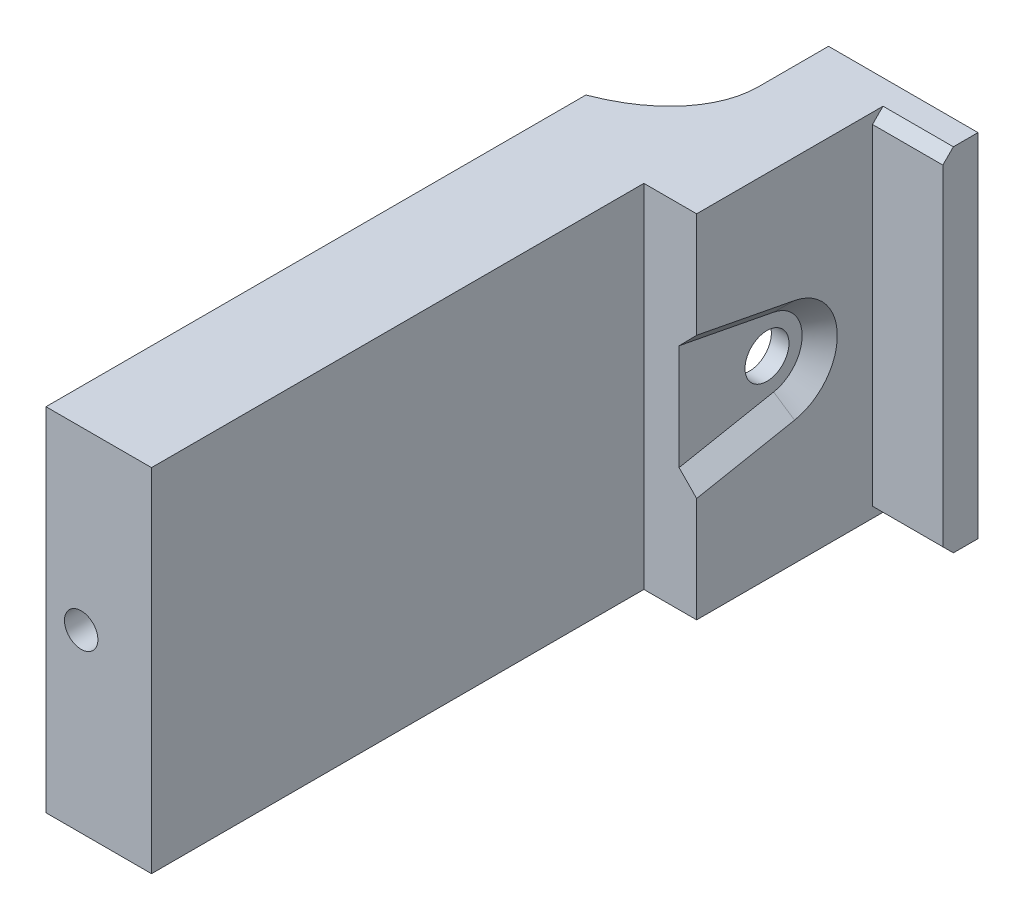
SolidWorks part; units mm, degrees
ref_plane "前视基准面" through (0, 0, 0) normal (0, 0, 1) x (1, 0, 0)
ref_plane "上视基准面" through (0, 0, 0) normal (0, 1, 0) x (1, 0, 0)
ref_plane "右视基准面" through (0, 0, 0) normal (1, 0, 0) x (0, 0, -1)
other "Configuration Table"
sketch "草图1" plane through (0, 0, 0) normal (0, 1, 0) x (1, 0, 0)
  line L0 (0, 0) -> (3, 0)
  line L1 (3, 0) -> (3, 10)
  line L2 (3, 10) -> (1, 10)
  line L3 (1, 10) -> (1, 2)
  line L4 (1, 2) -> (-2, 2)
  line L6 (-2, -26) -> (-6, -26)
  line L7 (-6, -26) -> (-6, -28)
  line L8 (-6, -28) -> (0, -28)
  line L9 (0, -28) -> (0, 0)
  line L12 (-2, 2) -> (-2, -26)
  dimension "D1" = 8
  dimension "D2" = 4
  dimension "D3" = 28
  dimension "D4" = 2
  dimension "D5" = 2
  dimension "D6" = 3
  dimension "D7" = 2
  dimension "D8" = 2
extrude "凸台-拉伸1" add sketch "草图1" along normal mid plane 20
sketch "草图2" plane through (1, 0, 0) normal (-1, 0, 0) x (0, 0, 1)
  line L0 (-5, 17.2009) -> (-5, -18.1104) construction
  line L2 (0, 0) -> (-13.8262, 0) construction
  line L3 (-2, 10) -> (-2, -10) construction
  circle A0 centre (-5, 0) radius 1.25
  dimension "D2" = 2.5
  dimension "D1" = 3
extrude "切除-拉伸1" cut sketch "草图2" against normal blind 15
sketch "草图4" plane through (0, 0, 28) normal (0, 0, 1) x (1, 0, 0)
  line L0 (-6, 0) -> (6.5775, 0) construction
  line L1 (-6, 10) -> (-6, -10) construction
  line L2 (-4, 12.0932) -> (-4, -13.8811) construction
  circle A0 centre (-4, 0) radius 0.95
  dimension "D2" = 1.9
  dimension "D1" = 2
extrude "切除-拉伸2" cut sketch "草图4" against normal through all
sketch "草图5" plane through (0, 0, 26) normal (0, 0, -1) x (-1, 0, 0)
  line L0 (2, 10) -> (6, 10)
  line L1 (6, 10) -> (6, -10) construction
  line L2 (2, 10) -> (6, 10) construction
  line L3 (6, 10) -> (2, 6)
  line L4 (2, 10) -> (2, -10) construction
  line L5 (2, 6) -> (2, 10)
  line L6 (0, 0) -> (10.5459, 0) construction
  line L7 (2, -6) -> (2, -10)
  line L8 (6, -10) -> (2, -6)
  line L9 (2, -10) -> (6, -10)
  dimension "D1" = 45
extrude "凸台-拉伸2" add sketch "草图5" along normal up to surface (28 mm away) up to face at (-0.5, 0, -2)
sketch "草图7" plane through (0, 0, -10) normal (0, 0, -1) x (-1, 0, 0)
  line L0 (-1, -10) -> (6, -10) construction
  line L1 (-1, 10) -> (-7, 10)
  line L2 (-1, 10) -> (-1, -10)
  line L3 (-1, -10) -> (-7, -10)
  line L4 (-7, 10) -> (-7, -10)
  line L5 (-1, 10) -> (-1, -10) construction
  dimension "D1" = 6
extrude "凸台-拉伸4" add sketch "草图7" along normal blind 2
chamfer "倒角1" distance 0.6 angle 45 2 edges at (5, -10, -10) (5, 10, -10)
sketch "草图8" plane through (0, 0, -2) normal (0, 0, -1) x (-1, 0, 0)
  line L0 (-1, 10) -> (1.5, 10)
  line L1 (-1, 10) -> (6, 10) construction
  line L2 (1.5, 10) -> (-1, 7.5)
  line L3 (-1, 10) -> (-1, -10) construction
  line L4 (-1, 7.5) -> (-1, 10)
  line L5 (-8.3664, 0) -> (9.2819, 0) construction
  line L6 (-1, -7.5) -> (-1, -10)
  line L7 (1.5, -10) -> (-1, -7.5)
  line L8 (-1, -10) -> (1.5, -10)
  dimension "D1" = 2.5
  dimension "D2" = 45
extrude "凸台-拉伸5" add sketch "草图8" along normal up to surface (10 mm away) up to face at (4, 0, -12)
fillet "圆角2" radius 6 2 edges at (-0.25, -8.75, -2) (-0.25, 8.75, -2)
sketch "草图9" plane through (3, 0, 0) normal (1, 0, 0) x (0, 0, -1)
  line L0 (0, -3) -> (0, 3)
  line L1 (0, 10) -> (0, -10) construction
  line L2 (0, 10) -> (0, -10) construction
  line L3 (0, 3) -> (5.3783, 1.9639)
  line L4 (-1.0602, 0) -> (1.3342, 0) construction
  line L5 (0, -3) -> (5.3783, -1.9639)
  arc A0 (5.3783, -1.9639) -> (5.3783, 1.9639) centre (5, 0) ccw
  point P14 (0, 0)
  dimension "D1" = 4
  dimension "D2" = 6
extrude "切除-拉伸3" cut sketch "草图9" against normal blind 1
chamfer "倒角2" distance 1 angle 45 3 edges at (3, -2.4819, -2.6892) (3, 0, -7) (3, 2.4819, -2.6892)
